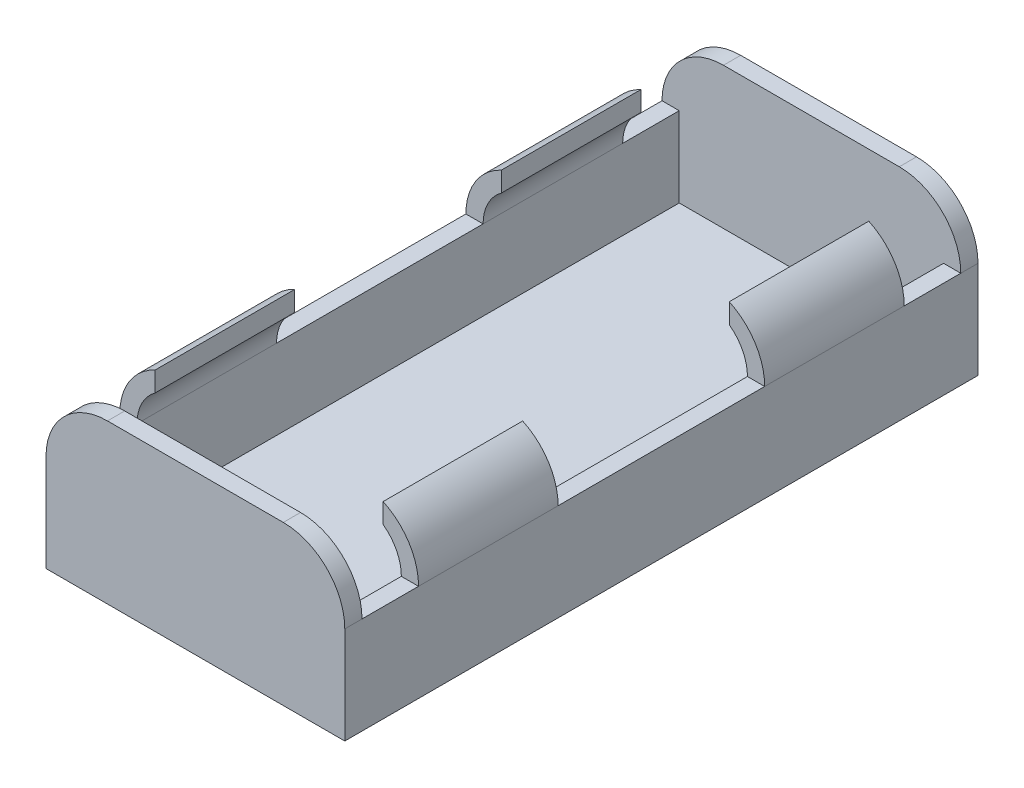
SolidWorks part; units mm, degrees
ref_plane "Front Plane" through (0, 0, 0) normal (0, 0, 1) x (1, 0, 0)
ref_plane "Top Plane" through (0, 0, 0) normal (0, 1, 0) x (1, 0, 0)
ref_plane "Right Plane" through (0, 0, 0) normal (1, 0, 0) x (0, 0, -1)
sketch "Sketch1" plane through (0, 0, 0) normal (0, 0, 1) x (1, 0, 0)
  line L1 (-12.15, 6.45) -> (12.15, 6.45)
  line L2 (-12.15, 6.45) -> (-12.15, -6.45)
  line L3 (-12.15, -6.45) -> (12.15, -6.45)
  line L4 (12.15, 6.45) -> (12.15, -6.45)
  line L5 (-12.15, 6.45) -> (12.15, -6.45) construction
  line L6 (-12.15, -6.45) -> (12.15, 6.45) construction
  point P0 (0, 0)
  dimension "D1" = 24.3
  dimension "D2" = 12.9
extrude "Boss-Extrude1" add sketch "Sketch1" along normal blind 51.5
fillet "Fillet1" radius 5 2 edges at (-12.15, 6.45, 25.75) (12.15, 6.45, 25.75)
shell "Shell1" thickness 1.4 removed face at (0, 6.45, 25.75)
sketch "Sketch2" plane through (0, 6.45, 0) normal (0, 1, 0) x (1, 0, 0)
  line L0 (-10.75, -50.1) -> (10.75, -50.1) construction
  line L1 (-9.2696, -1.4) -> (9.2696, -1.4)
  line L2 (-9.2696, -1.4) -> (-9.2696, -50.1)
  line L3 (-9.2696, -50.1) -> (9.2696, -50.1)
  line L4 (9.2696, -1.4) -> (9.2696, -50.1)
  line L5 (-9.2696, -1.4) -> (9.2696, -50.1) construction
  line L6 (-9.2696, -50.1) -> (9.2696, -1.4) construction
  point P0 (0, -25.75)
extrude "Cut-Extrude1" cut sketch "Sketch2" against normal blind 5
sketch "Sketch3" plane through (0, 6.45, 0) normal (0, 1, 0) x (1, 0, 0)
  line L0 (-12.15, -51.5) -> (-12.15, 0) construction
  line L1 (-12.15, -1.4) -> (12.15, -1.4)
  line L2 (-12.15, -1.4) -> (-12.15, -6)
  line L3 (-12.15, -6) -> (12.15, -6)
  line L4 (12.15, -1.4) -> (12.15, -6)
  line L5 (12.15, 0) -> (12.15, -51.5) construction
  line L6 (7.15, -1.4) -> (-7.15, -1.4) construction
  line L7 (-12.15, -25.75) -> (12.15, -25.75) construction
  line L8 (12.15, -50.1) -> (12.15, -45.5)
  line L9 (-12.15, -45.5) -> (12.15, -45.5)
  line L10 (-12.15, -50.1) -> (-12.15, -45.5)
  line L11 (-12.15, -50.1) -> (12.15, -50.1)
  line L13 (-12.15, -17.35) -> (12.15, -17.35)
  line L14 (-12.15, -17.35) -> (-12.15, -34.15)
  line L15 (-12.15, -34.15) -> (12.15, -34.15)
  line L16 (12.15, -17.35) -> (12.15, -34.15)
  line L17 (-12.15, -17.35) -> (12.15, -34.15) construction
  line L18 (-12.15, -34.15) -> (12.15, -17.35) construction
  point P16 (0, -25.75)
  dimension "D1" = 4.6
  dimension "D2" = 16.8
extrude "Cut-Extrude2" cut sketch "Sketch3" against normal up to vertex (5 mm away) up to point (12.15, 1.45, 0)
